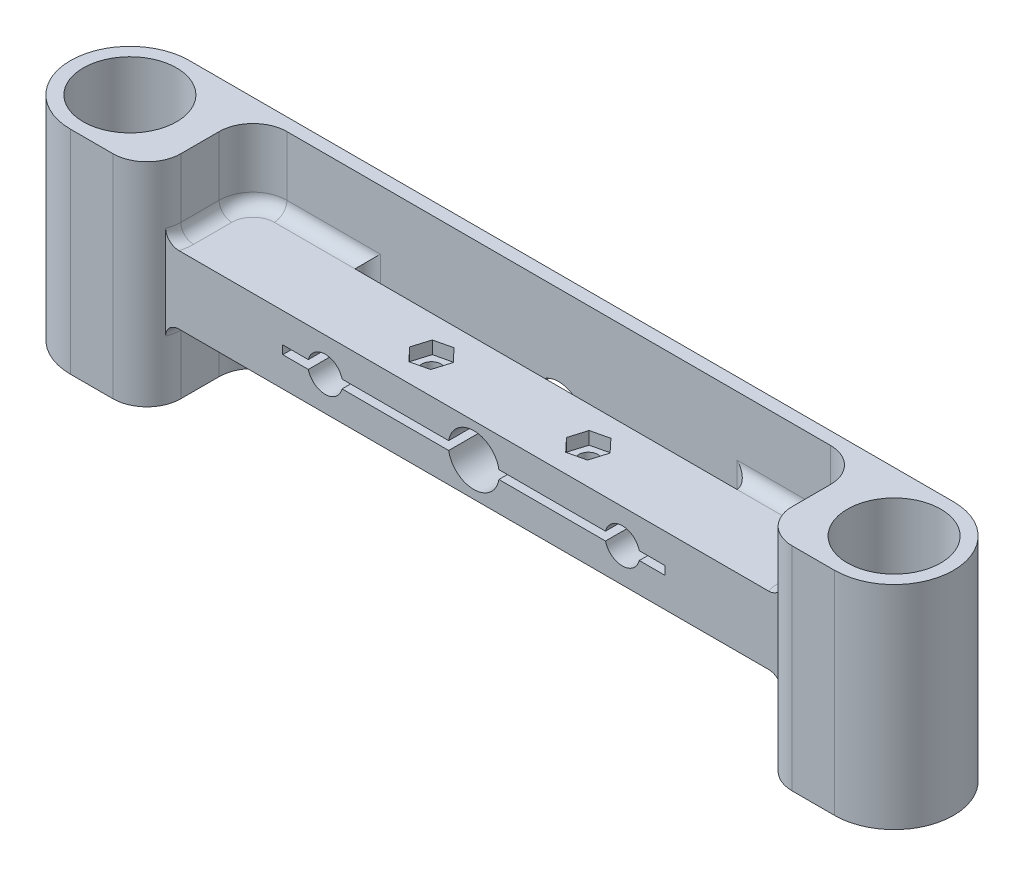
SolidWorks part; units mm, degrees
ref_plane "Front Plane" through (0, 0, 0) normal (0, 0, 1) x (1, 0, 0)
ref_plane "Top Plane" through (0, 0, 0) normal (0, 1, 0) x (1, 0, 0)
ref_plane "Right Plane" through (0, 0, 0) normal (1, 0, 0) x (0, 0, -1)
sketch "Sketch1" plane through (0, 0, 0) normal (0, 1, 0) x (1, 0, 0)
  line L0 (137.4606, -14.5) -> (119.4606, -14.5)
  line L1 (119.4606, -14.5) -> (119.4606, 10.5)
  line L2 (-42.5394, -14.5) -> (-24.5394, -14.5)
  line L3 (-42.5394, 13.5) -> (137.4606, 13.5)
  line L4 (119.4606, 10.5) -> (-24.5394, 10.5)
  line L5 (-24.5394, -14.5) -> (-24.5394, 10.5)
  circle A0 centre (-42.5394, -0.5) radius 11
  circle A1 centre (137.4606, -0.5) radius 11
  arc A2 (-42.5394, -14.5) -> (-42.5394, 13.5) centre (-42.5394, -0.5) cw
  arc A6 (137.4606, 13.5) -> (137.4606, -14.5) centre (137.4606, -0.5) cw
  dimension "D3" = 22
  dimension "D4" = 22
  dimension "D5" = 180
  dimension "D6" = 3
  dimension "D1" = 18
  dimension "D2" = 18
  dimension "D8" = 3
extrude "Boss-Extrude1" add sketch "Sketch1" along normal blind 100
fillet "Fillet1" radius 8 4 edges at (119.4606, 50, -10.5) (119.4606, 50, 14.5) (-24.5394, 50, -10.5) (-24.5394, 50, 14.5)
sketch "Sketch2" plane through (0, 0, -10.5) normal (0, 0, 1) x (1, 0, 0)
  line L0 (47.4606, 100) -> (47.4606, 0) construction
  line L1 (-16.5394, 100) -> (111.4606, 100) construction
  line L2 (-16.5394, 0) -> (111.4606, 0) construction
  circle A0 centre (12.4606, 50) radius 4.1
  circle A1 centre (82.4606, 50) radius 4.1
  circle A2 centre (47.4606, 50) radius 6
  point P10 (47.4606, 50)
  dimension "D1" = 8.2
  dimension "D2" = 8.2
  dimension "D5" = 12
  dimension "D3" = 35
  dimension "D4" = 35
extrude "Cut-Extrude1" cut sketch "Sketch2" against normal blind 10
sketch "Sketch3" plane through (0, 0, -10.5) normal (0, 0, 1) x (1, 0, 0)
  line L0 (12.4606, 58) -> (82.4606, 58)
  line L1 (12.4606, 42) -> (82.4606, 42)
  line L2 (12.4606, 58) -> (-16.5394, 58)
  line L3 (-16.5394, 100) -> (-16.5394, 0) construction
  line L4 (-16.5394, 58) -> (-28.8663, 58)
  line L5 (-28.8663, 58) -> (-28.8663, 42)
  line L6 (-28.8663, 42) -> (12.4606, 42)
  line L7 (82.4606, 58) -> (124.1494, 58)
  line L8 (124.1494, 58) -> (124.1494, 42)
  line L9 (124.1494, 42) -> (82.4606, 42)
  circle A2 centre (12.4606, 50) radius 4.1
  circle A3 centre (82.4606, 50) radius 4.1
  circle A4 centre (47.4606, 50) radius 6
  dimension "D2" = 12
extrude "Boss-Extrude2" add sketch "Sketch3" along normal blind 20
fillet "Fillet2" radius 3 14 edges at (-24.6867, 42, 8.0281) (-24.5394, 42, 2) (-22.1963, 42, -8.1569) (119.6079, 42, 8.0281) (119.4606, 42, 2) (117.1174, 42, -8.1569) (119.6079, 58, 8.0281) (119.4606, 58, 2) (-24.6867, 58, 8.0281) (-24.5394, 58, 2) (-22.1963, 58, -8.1569) (47.4606, 58, -10.5) (47.4606, 42, -10.5) (117.1174, 58, -8.1569)
sketch "Sketch4" plane through (0, 0, 9.5) normal (0, 0, 1) x (1, 0, 0)
  line L0 (47.4606, 50) -> (2.4606, 50)
  line L1 (47.4606, 50) -> (92.4606, 50)
  dimension "D1" = 45
extrude "Cut-Extrude-Thin1" cut sketch "Sketch4" against normal up to surface (20 mm away) and the other way through all thin up to face at (47.4606, 19.5, -10.5) thin type mid plane wall 2
sketch "Sketch5" plane through (0, 42, 0) normal (0, -1, 0) x (-1, 0, 0)
  line L0 (-2.4606, 7.5) -> (-47.4606, 7.5)
  line L1 (16.5394, 7.5) -> (-111.4606, 7.5) construction
  line L2 (-47.4606, 7.5) -> (-92.4606, 7.5)
  dimension "D1" = 45
  dimension "D2" = 45
extrude "Cut-Extrude-Thin2" cut sketch "Sketch5" against normal blind 20 and the other way through all thin thin type one direction wall 3
fillet "Fillet3" radius 3 2 edges at (92.4606, 50, -10.5) (2.4606, 50, -10.5)
sketch "Sketch6" plane through (0, 49, 0) normal (0, 1, 0) x (1, 0, 0)
  line L0 (16.4368, 7.5) -> (41.5445, -9.5) construction
  line L1 (41.5445, -9.5) -> (53.3767, -9.5) construction
  line L2 (53.3767, -9.5) -> (78.4844, 7.5) construction
  circle A0 centre (28.9906, -1) radius 2.25
  circle A1 centre (65.9305, -1) radius 2.25
  dimension "D1" = 4.5
  dimension "D2" = 4.5
extrude "Cut-Extrude2" cut sketch "Sketch6" against normal through all both and the other way through all
sketch "Sketch7" plane through (0, 58, 0) normal (0, 1, 0) x (1, 0, 0)
  line L1 (33.1506, -0.0263) -> (30.2274, 3.0895)
  line L2 (30.2274, 3.0895) -> (26.0674, 2.1158)
  line L3 (26.0674, 2.1158) -> (24.8307, -1.9737)
  line L4 (24.8307, -1.9737) -> (27.7539, -5.0895)
  line L5 (27.7539, -5.0895) -> (31.9138, -4.1158)
  line L6 (31.9138, -4.1158) -> (33.1506, -0.0263)
  line L7 (70.0905, -0.0263) -> (67.1673, 3.0895)
  line L8 (67.1673, 3.0895) -> (63.0073, 2.1158)
  line L9 (63.0073, 2.1158) -> (61.7706, -1.9737)
  line L10 (61.7706, -1.9737) -> (64.6938, -5.0895)
  line L11 (64.6938, -5.0895) -> (68.8537, -4.1158)
  line L12 (68.8537, -4.1158) -> (70.0905, -0.0263)
  circle A0 centre (28.9906, -1) radius 3.7 construction
  circle A1 centre (65.9305, -1) radius 3.7 construction
  dimension "D1" = 7.4
  dimension "D2" = 7.4
extrude "Cut-Extrude3" cut sketch "Sketch7" against normal blind 3
sketch "Sketch8" plane through (0, 100, 0) normal (0, 1, 0) x (1, 0, 0)
  line L6 (119.4606, 2.5) -> (119.4606, -6.5)
  line L7 (127.4606, -14.5) -> (137.4606, -14.5)
  line L8 (137.4606, 13.5) -> (-42.5394, 13.5)
  line L9 (-42.5394, -14.5) -> (-32.5394, -14.5)
  line L10 (-24.5394, -6.5) -> (-24.5394, 2.5)
  line L11 (-16.5394, 10.5) -> (111.4606, 10.5)
  line L12 (119.4606, 2.5) -> (119.4606, -6.5)
  line L13 (127.4606, -14.5) -> (137.4606, -14.5)
  line L14 (137.4606, 13.5) -> (-42.5394, 13.5)
  line L15 (-42.5394, -14.5) -> (-32.5394, -14.5)
  line L16 (-24.5394, -6.5) -> (-24.5394, 2.5)
  line L17 (-16.5394, 10.5) -> (111.4606, 10.5)
  arc A6 (119.4606, -6.5) -> (127.4606, -14.5) centre (127.4606, -6.5) ccw
  arc A7 (137.4606, -14.5) -> (137.4606, 13.5) centre (137.4606, -0.5) ccw
  arc A8 (-42.5394, 13.5) -> (-42.5394, -14.5) centre (-42.5394, -0.5) ccw
  arc A9 (-32.5394, -14.5) -> (-24.5394, -6.5) centre (-32.5394, -6.5) ccw
  arc A10 (-16.5394, 10.5) -> (-24.5394, 2.5) centre (-16.5394, 2.5) ccw
  arc A11 (119.4606, 2.5) -> (111.4606, 10.5) centre (111.4606, 2.5) ccw
  arc A12 (119.4606, -6.5) -> (127.4606, -14.5) centre (127.4606, -6.5) ccw
  arc A13 (137.4606, -14.5) -> (137.4606, 13.5) centre (137.4606, -0.5) ccw
  arc A14 (-42.5394, 13.5) -> (-42.5394, -14.5) centre (-42.5394, -0.5) ccw
  arc A15 (-32.5394, -14.5) -> (-24.5394, -6.5) centre (-32.5394, -6.5) ccw
  arc A16 (-16.5394, 10.5) -> (-24.5394, 2.5) centre (-16.5394, 2.5) ccw
  arc A17 (119.4606, 2.5) -> (111.4606, 10.5) centre (111.4606, 2.5) ccw
  dimension "D1" = 0
extrude "Cut-Extrude4" cut sketch "Sketch8" against normal blind 25
sketch "Sketch9" plane through (0, 0, 0) normal (0, 1, 0) x (1, 0, 0)
  line L6 (127.4606, -14.5) -> (137.4606, -14.5)
  line L7 (119.4606, 2.5) -> (119.4606, -6.5)
  line L8 (-16.5394, 10.5) -> (111.4606, 10.5)
  line L9 (-24.5394, -6.5) -> (-24.5394, 2.5)
  line L10 (-42.5394, -14.5) -> (-32.5394, -14.5)
  line L11 (137.4606, 13.5) -> (-42.5394, 13.5)
  line L12 (127.4606, -14.5) -> (137.4606, -14.5)
  line L13 (119.4606, 2.5) -> (119.4606, -6.5)
  line L14 (-16.5394, 10.5) -> (111.4606, 10.5)
  line L15 (-24.5394, -6.5) -> (-24.5394, 2.5)
  line L16 (-42.5394, -14.5) -> (-32.5394, -14.5)
  line L17 (137.4606, 13.5) -> (-42.5394, 13.5)
  arc A6 (119.4606, -6.5) -> (127.4606, -14.5) centre (127.4606, -6.5) ccw
  arc A7 (119.4606, 2.5) -> (111.4606, 10.5) centre (111.4606, 2.5) ccw
  arc A8 (-16.5394, 10.5) -> (-24.5394, 2.5) centre (-16.5394, 2.5) ccw
  arc A9 (-32.5394, -14.5) -> (-24.5394, -6.5) centre (-32.5394, -6.5) ccw
  arc A10 (-42.5394, 13.5) -> (-42.5394, -14.5) centre (-42.5394, -0.5) ccw
  arc A11 (137.4606, -14.5) -> (137.4606, 13.5) centre (137.4606, -0.5) ccw
  arc A12 (119.4606, -6.5) -> (127.4606, -14.5) centre (127.4606, -6.5) ccw
  arc A13 (119.4606, 2.5) -> (111.4606, 10.5) centre (111.4606, 2.5) ccw
  arc A14 (-16.5394, 10.5) -> (-24.5394, 2.5) centre (-16.5394, 2.5) ccw
  arc A15 (-32.5394, -14.5) -> (-24.5394, -6.5) centre (-32.5394, -6.5) ccw
  arc A16 (-42.5394, 13.5) -> (-42.5394, -14.5) centre (-42.5394, -0.5) ccw
  arc A17 (137.4606, -14.5) -> (137.4606, 13.5) centre (137.4606, -0.5) ccw
  dimension "D1" = 0
extrude "Cut-Extrude5" cut sketch "Sketch9" along normal blind 25
